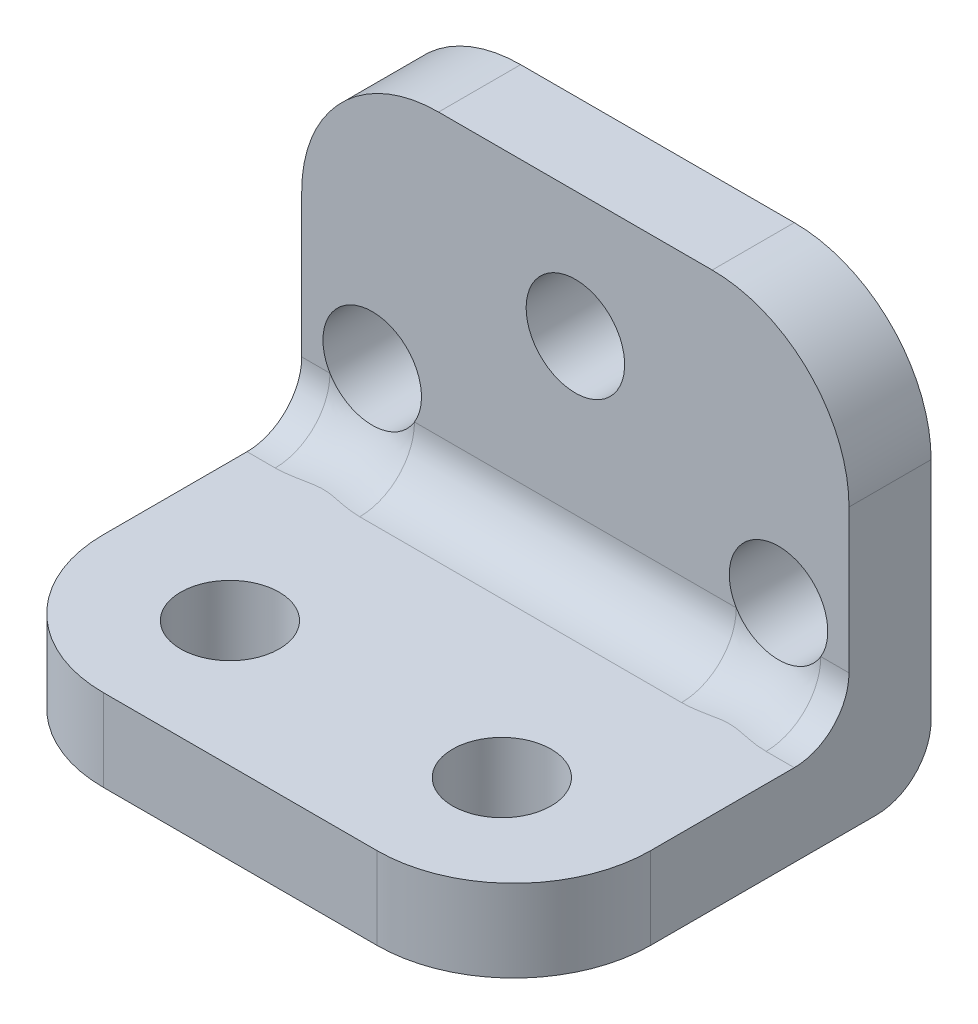
SolidWorks part; units mm, degrees
ref_plane "Alzado" through (0, 0, 0) normal (0, 0, 1) x (1, 0, 0)
ref_plane "Planta" through (0, 0, 0) normal (0, 1, 0) x (1, 0, 0)
ref_plane "Vista lateral" through (0, 0, 0) normal (1, 0, 0) x (0, 0, -1)
sketch "Croquis1" plane through (0, 0, 0) normal (0, 1, 0) x (1, 0, 0)
  line L1 (-10, 7.625) -> (10, 7.625)
  line L2 (-10, 7.625) -> (-10, -7.625)
  line L3 (-10, -7.625) -> (10, -7.625)
  line L4 (10, 7.625) -> (10, -7.625)
  line L5 (-10, 7.625) -> (10, -7.625) construction
  line L6 (-10, -7.625) -> (10, 7.625) construction
  point P0 (0, 0)
  dimension "D1" = 20
  dimension "D2" = 15.25
extrude "Saliente-Extruir1" add sketch "Croquis1" along normal blind 3
sketch "Croquis2" plane through (0, 3, 0) normal (0, 1, 0) x (1, 0, 0)
  line L0 (-10, 7.625) -> (-10, -7.625) construction
  line L1 (10, 7.625) -> (-10, 7.625)
  line L2 (10, 7.625) -> (10, 4.625)
  line L3 (10, 4.625) -> (-10, 4.625)
  line L4 (-10, 7.625) -> (-10, 4.625)
  dimension "D1" = 3
extrude "Saliente-Extruir2" add sketch "Croquis2" along normal blind 12.25
sketch "Croquis3" plane through (0, 0, 0) normal (0, -1, 0) x (1, 0, 0)
  line L0 (10, 3.0313) -> (-10, 3.0313) construction
  line L1 (10, 7.625) -> (10, -7.625) construction
  line L2 (-10, -7.625) -> (-10, 7.625) construction
  line L3 (0, 7.625) -> (0, -7.625) construction
  line L4 (-10, 7.625) -> (10, 7.625) construction
  line L5 (10, -7.625) -> (-10, -7.625) construction
  line L6 (-10, 7.625) -> (10, 7.625) construction
  circle A0 centre (4.9689, 3.0313) radius 1.8
  circle A1 centre (-4.9689, 3.0313) radius 1.8
  dimension "D1" = 3.6
  dimension "D2" = 4.5938
extrude "Cortar-Extruir1" cut sketch "Croquis3" against normal blind 20
sketch "Croquis4" plane through (0, 0, -7.625) normal (0, 0, -1) x (-1, 0, 0)
  line L0 (-10, 10.6562) -> (10, 10.6562) construction
  line L1 (-10, 15.25) -> (-10, 0) construction
  line L2 (10, 15.25) -> (-10, 15.25) construction
  line L3 (10, 5.9246) -> (-10, 5.9246) construction
  line L4 (10, 15.25) -> (10, 0) construction
  line L5 (0, 15.25) -> (0, 0) construction
  line L6 (-10, 15.25) -> (10, 15.25) construction
  line L7 (7.4246, 15.25) -> (7.4246, 0) construction
  line L8 (-10, 0) -> (10, 0) construction
  line L9 (-7.4246, 15.25) -> (-7.4246, 0) construction
  line L10 (10, -1.5) -> (-10, -1.5) construction
  line L11 (7.4246, 5.9246) -> (0, -1.5) construction
  line L12 (0, -1.5) -> (-7.4246, 5.9246) construction
  circle A0 centre (0, 10.6562) radius 1.8
  circle A1 centre (7.4246, 5.9246) radius 1.8
  circle A2 centre (-7.4246, 5.9246) radius 1.8
  circle A3 centre (0, -1.5) radius 10.5 construction
  dimension "D1" = 3.6
  dimension "D3" = 21
  dimension "D2" = 4.5938
  dimension "D4" = 1.5
  dimension "D5" = 45
extrude "Cortar-Extruir2" cut sketch "Croquis4" against normal blind 20
fillet "Redondeo1" radius 5 4 edges at (-10, 15.25, -6.125) (10, 1.5, 7.625) (-10, 1.5, 7.625) (10, 15.25, -6.125)
fillet "Redondeo2" radius 2 2 edges at (0, 0, -7.625)
